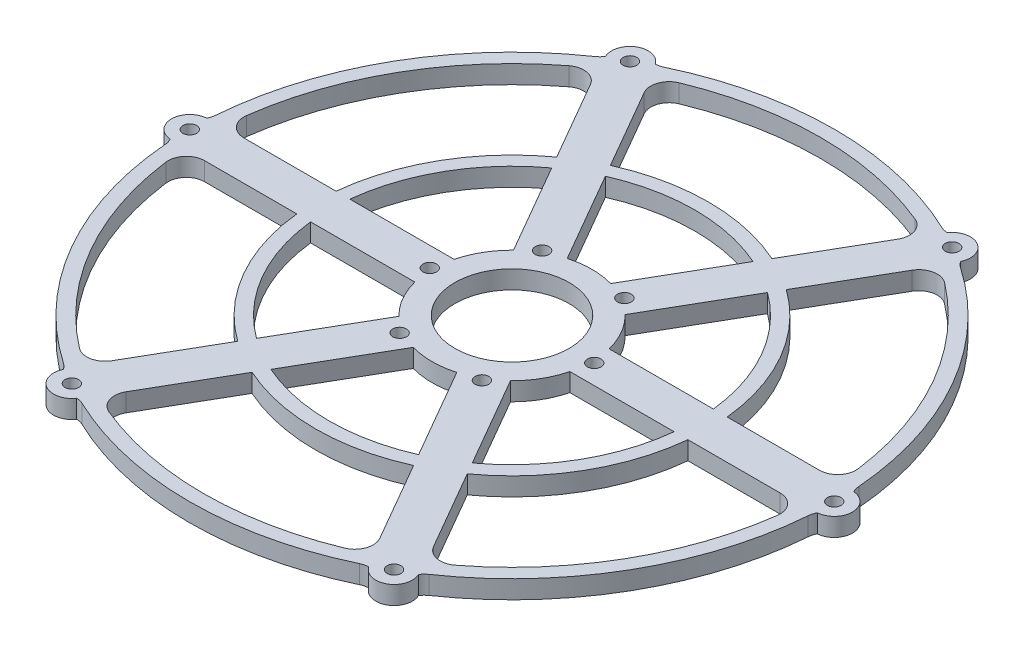
SolidWorks part; units mm, degrees
ref_plane "前视基准面" through (0, 0, 0) normal (0, 0, 1) x (1, 0, 0)
ref_plane "上视基准面" through (0, 0, 0) normal (0, 1, 0) x (1, 0, 0)
ref_plane "右视基准面" through (0, 0, 0) normal (1, 0, 0) x (0, 0, -1)
sketch "草图1" plane through (0, 0, 0) normal (0, 1, 0) x (1, 0, 0)
  line L12 (-35.25, -61.0548) -> (0, 0) construction
  line L13 (-67.3629, 4.3002) -> (-9.579, 4.3002)
  line L14 (-67.3629, -4.3002) -> (-9.579, -4.3002)
  line L15 (9.579, 4.3002) -> (67.3629, 4.3002)
  line L16 (9.579, -4.3002) -> (67.3629, -4.3002)
  line L17 (1.0654, -10.4458) -> (29.9573, -60.4881)
  line L18 (8.5136, -6.1456) -> (37.4056, -56.1878)
  line L19 (-29.9573, 60.4881) -> (-1.0654, 10.4458)
  line L20 (-37.4056, 56.1878) -> (-8.5136, 6.1456)
  line L21 (-8.5136, -6.1456) -> (-37.4056, -56.1878)
  line L22 (-1.0654, -10.4458) -> (-29.9573, -60.4881)
  line L23 (37.4056, 56.1878) -> (8.5136, 6.1456)
  line L24 (29.9573, 60.4881) -> (1.0654, 10.4458)
  line L25 (-9.579, 4.3002) -> (-67.3629, 4.3002)
  line L26 (-9.579, -4.3002) -> (-67.3629, -4.3002)
  line L27 (67.3629, -4.3002) -> (9.579, -4.3002)
  line L28 (67.3629, 4.3002) -> (9.579, 4.3002)
  line L29 (-1.0654, 10.4458) -> (-29.9573, 60.4881)
  line L30 (-8.5136, 6.1456) -> (-37.4056, 56.1878)
  line L31 (29.9573, -60.4881) -> (1.0654, -10.4458)
  line L32 (37.4056, -56.1878) -> (8.5136, -6.1456)
  line L33 (8.5136, 6.1456) -> (37.4056, 56.1878)
  line L34 (1.0654, 10.4458) -> (29.9573, 60.4881)
  line L35 (-37.4056, -56.1878) -> (-8.5136, -6.1456)
  line L36 (-29.9573, -60.4881) -> (-1.0654, -10.4458)
  line L37 (10.5, 0) -> (70.5, 0) construction
  line L38 (-10.5, 0) -> (9.5, 0) construction
  arc A0 (-7.8594, 1.4934) -> (-7.8594, -1.4934) centre (0, 0) ccw construction
  circle A1 centre (-8, 0) radius 1.5
  circle A2 centre (0, 8) radius 1.5
  circle A3 centre (8, 0) radius 1.5
  circle A4 centre (0, -8) radius 1.5
  arc A5 (-8.5136, 6.1456) -> (-9.579, 4.3002) centre (0, 0) ccw
  arc A6 (-67.3629, -4.3002) -> (-37.4056, -56.1878) centre (0, 0) ccw
  arc A7 (-70.5, 3) -> (-70.5, -3) centre (-70.5, 0) ccw
  circle A8 centre (-70.5, 0) radius 1.5
  arc A9 (-32.6519, 62.5548) -> (-37.8481, 59.5548) centre (-35.25, 61.0548) ccw
  circle A10 centre (-35.25, 61.0548) radius 1.5
  arc A11 (37.8481, 59.5548) -> (32.6519, 62.5548) centre (35.25, 61.0548) ccw
  circle A12 centre (35.25, 61.0548) radius 1.5
  arc A13 (70.5, -3) -> (70.5, 3) centre (70.5, 0) ccw
  circle A14 centre (70.5, 0) radius 1.5
  arc A15 (32.6519, -62.5548) -> (37.8481, -59.5548) centre (35.25, -61.0548) ccw
  circle A16 centre (35.25, -61.0548) radius 1.5
  arc A17 (-37.8481, -59.5548) -> (-32.6519, -62.5548) centre (-35.25, -61.0548) ccw
  circle A18 centre (-35.25, -61.0548) radius 1.5
  arc A21 (1.4934, 7.8594) -> (-6.746, 4.3002) centre (0, 0) ccw construction
  arc A22 (-1.4934, -7.8594) -> (1.4934, -7.8594) centre (0, 0) ccw construction
  arc A23 (7.8594, -1.4934) -> (6.746, 4.3002) centre (0, 0) ccw construction
  circle A24 centre (0, 0) radius 4.5
  arc A25 (1.0654, 10.4458) -> (-1.0654, 10.4458) centre (0, 0) ccw
  arc A26 (9.579, 4.3002) -> (8.5136, 6.1456) centre (0, 0) ccw
  arc A27 (8.5136, -6.1456) -> (9.579, -4.3002) centre (0, 0) ccw
  arc A28 (-1.0654, -10.4458) -> (1.0654, -10.4458) centre (0, 0) ccw
  arc A29 (-9.579, -4.3002) -> (-8.5136, -6.1456) centre (0, 0) ccw
  arc A30 (-37.4056, 56.1878) -> (-67.3629, 4.3002) centre (0, 0) ccw
  arc A31 (29.9573, 60.4881) -> (-29.9573, 60.4881) centre (0, 0) ccw
  arc A32 (67.3629, 4.3002) -> (37.4056, 56.1878) centre (0, 0) ccw
  arc A33 (37.4056, -56.1878) -> (67.3629, -4.3002) centre (0, 0) ccw
  arc A34 (-29.9573, -60.4881) -> (29.9573, -60.4881) centre (0, 0) ccw
  arc A35 (32.6519, 62.5548) -> (-32.6519, 62.5548) centre (0, 0) ccw
  arc A36 (70.5, 3) -> (37.8481, 59.5548) centre (0, 0) ccw
  arc A37 (37.8481, -59.5548) -> (70.5, -3) centre (0, 0) ccw
  arc A38 (-32.6519, -62.5548) -> (32.6519, -62.5548) centre (0, 0) ccw
  arc A39 (-70.5, -3) -> (-37.8481, -59.5548) centre (0, 0) ccw
  arc A40 (-37.8481, 59.5548) -> (-70.5, 3) centre (0, 0) ccw
  point P14 (0, 0)
  point P15 (0, 0)
  point P52 (0, 0)
  point P111 (0, 0)
  point P135 (0, 0)
  dimension "D1" = 16
  dimension "D2" = 3
  dimension "D4" = 2.5
  dimension "D5" = 135
  dimension "D6" = 6
  dimension "D7" = 3
  dimension "D9" = 9
  dimension "D8" = 6
  dimension "D3" = 4
  dimension "D10" = 6
extrude "凸台-拉伸1" add sketch "草图1" along normal blind 4 contours A9 A40 A7 A39 A17 A38 A15 A37 A13 A36 A11 A35 L14 A29 L21 A6 A1 A2 region at (-59.3453, 0, -34.263)
fillet "圆角1" radius 4 24 edges at (-37.4056, 2, 56.1878) (-67.3629, 2, 4.3002) (-70.5, 2, 3) (-70.5, 2, -3) (-67.3629, 2, -4.3002) (-37.4056, 2, -56.1878) (-29.9573, 2, -60.4881) (-37.8481, 2, -59.5548) (-32.6519, 2, -62.5548) (32.6519, 2, -62.5548) (29.9573, 2, -60.4881) (37.4056, 2, -56.1878) (37.8481, 2, -59.5548) (70.5, 2, -3) (70.5, 2, 3) (67.3629, 2, -4.3002) (67.3629, 2, 4.3002) (37.8481, 2, 59.5548) (37.4056, 2, 56.1878) (32.6519, 2, 62.5548) (29.9573, 2, 60.4881) (-37.8481, 2, 59.5548) (-29.9573, 2, 60.4881) (-32.6519, 2, 62.5548)
fillet "圆角2" radius 4 12 edges at (-1.0654, 2, 10.4458) (-8.5136, 2, 6.1456) (-9.579, 2, 4.3002) (-9.579, 2, -4.3002) (-8.5136, 2, -6.1456) (1.0654, 2, -10.4458) (-1.0654, 2, -10.4458) (9.579, 2, -4.3002) (8.5136, 2, -6.1456) (9.579, 2, 4.3002) (8.5136, 2, 6.1456) (1.0654, 2, 10.4458)
sketch "草图2" plane through (0, 0, 0) normal (0, -1, 0) x (-1, 0, 0)
  line L0 (23.0864, -63.4293) -> (23.5994, -64.8388)
  line L1 (0, 0) -> (0, -46.6688) construction
  line L2 (-23.0864, -63.4293) -> (-23.5994, -64.8388)
  line L3 (-43.3882, -51.708) -> (-44.3523, -52.8571)
  line L4 (-66.4745, -11.7213) -> (-67.9517, -11.9817)
  line L5 (-66.4745, 11.7213) -> (-67.9517, 11.9817)
  line L6 (-43.3882, 51.708) -> (-44.3523, 52.8571)
  line L7 (-23.0864, 63.4293) -> (-23.5994, 64.8388)
  line L8 (23.0864, 63.4293) -> (23.5994, 64.8388)
  line L9 (43.3882, 51.708) -> (44.3523, 52.8571)
  line L10 (66.4745, 11.7213) -> (67.9517, 11.9817)
  line L11 (66.4745, -11.7213) -> (67.9517, -11.9817)
  line L12 (43.3882, -51.708) -> (44.3523, -52.8571)
  arc A0 (-23.0864, -63.4293) -> (23.0864, -63.4293) centre (0, 0) ccw
  arc A1 (-23.5994, -64.8388) -> (23.5994, -64.8388) centre (0, 0) ccw
  arc A2 (-66.4745, -11.7213) -> (-43.3882, -51.708) centre (0, 0) ccw
  arc A3 (-67.9517, -11.9817) -> (-44.3523, -52.8571) centre (0, 0) ccw
  arc A4 (-43.3882, 51.708) -> (-66.4745, 11.7213) centre (0, 0) ccw
  arc A5 (-44.3523, 52.8571) -> (-67.9517, 11.9817) centre (0, 0) ccw
  arc A6 (23.0864, 63.4293) -> (-23.0864, 63.4293) centre (0, 0) ccw
  arc A7 (23.5994, 64.8388) -> (-23.5994, 64.8388) centre (0, 0) ccw
  arc A8 (66.4745, 11.7213) -> (43.3882, 51.708) centre (0, 0) ccw
  arc A9 (67.9517, 11.9817) -> (44.3523, 52.8571) centre (0, 0) ccw
  arc A10 (43.3882, -51.708) -> (66.4745, -11.7213) centre (0, 0) ccw
  arc A11 (44.3523, -52.8571) -> (67.9517, -11.9817) centre (0, 0) ccw
  point P30 (0, 0)
  dimension "D1" = 1.5
  dimension "D2" = 20
  dimension "D3" = 6
extrude "凸台-拉伸2" add sketch "草图2" along normal blind 5 and the other way blind 9
chamfer "倒角1" distance 0.5 angle 45 6 edges at (59.7558, -5, -34.5) (59.7558, -5, 34.5) (0, -5, 69) (-59.7558, -5, 34.5) (-59.7558, -5, -34.5) (0, -5, -69)
sketch "草图3" plane through (0, 4, 0) normal (0, 1, 0) x (1, 0, 0)
  circle A0 centre (0, 0) radius 40
  circle A1 centre (0, 0) radius 43
  dimension "D1" = 80
  dimension "D2" = 3
extrude "凸台-拉伸3" add sketch "草图3" against normal up to surface (4 mm away) up to face at (-42.1051, 0, 24.3094)
sketch "草图4" plane through (0, 4, 0) normal (0, 1, 0) x (1, 0, 0)
  circle A0 centre (0, 0) radius 12.5
  dimension "D1" = 25
extrude "切除-拉伸1" cut sketch "草图4" against normal blind 10
sketch "草图5" plane through (0, 4, 0) normal (0, 1, 0) x (1, 0, 0)
  circle A0 centre (0, 0) radius 12.5
  circle A1 centre (0, 0) radius 17.5
  dimension "D1" = 5
extrude "凸台-拉伸4" add sketch "草图5" against normal up to surface (4 mm away) up to face at (0, 0, 58.1881)
sketch "草图6" plane through (0, 0, 0) normal (0, -1, 0) x (1, 0, 0)
  line L0 (0, 0) -> (35.25, 61.0548) construction
  circle A0 centre (9, 15.5885) radius 1.5
  circle A1 centre (18, 0) radius 1.5
  circle A2 centre (9, -15.5885) radius 1.5
  circle A3 centre (-9, -15.5885) radius 1.5
  circle A4 centre (-18, 0) radius 1.5
  circle A5 centre (-9, 15.5885) radius 1.5
  point P18 (0, 0)
  dimension "D1" = 3
  dimension "D2" = 18
  dimension "D3" = 6
extrude "切除-拉伸2" cut sketch "草图6" against normal blind 9
sketch "草图7" plane through (0, 0, 0) normal (0, -1, 0) x (-1, 0, 0)
  circle A0 centre (0, 0) radius 99.6246
extrude "切除-拉伸3" cut sketch "草图7" along normal blind 33
sketch "草图8" plane through (0, 4, 0) normal (0, 1, 0) x (1, 0, 0)
  circle A0 centre (0, 0) radius 104.7007
extrude "切除-拉伸4" cut sketch "草图8" along normal blind 205
sketch "草图9" plane through (0, 0, 0) normal (0, -1, 0) x (-1, 0, 0)
  circle A0 centre (35.25, 61.0548) radius 4
  circle A1 centre (70.5, 0) radius 4
  circle A2 centre (35.25, -61.0548) radius 4
  circle A3 centre (-35.25, -61.0548) radius 4
  circle A4 centre (-70.5, 0) radius 4
  circle A5 centre (-35.25, 61.0548) radius 4
  circle A6 centre (35.25, 61.0548) radius 1.5
  circle A7 centre (70.5, 0) radius 1.5
  circle A8 centre (35.25, -61.0548) radius 1.5
  circle A9 centre (-35.25, -61.0548) radius 1.5
  circle A10 centre (-70.5, 0) radius 1.5
  circle A11 centre (-35.25, 61.0548) radius 1.5
  point P15 (0, 0)
  point P27 (0, 0)
  dimension "D1" = 8
  dimension "D2" = 6
  dimension "D3" = 6
extrude "凸台-拉伸5" add sketch "草图9" against normal up to surface (4 mm away) up to face at (-9, 4, 17.0885)
